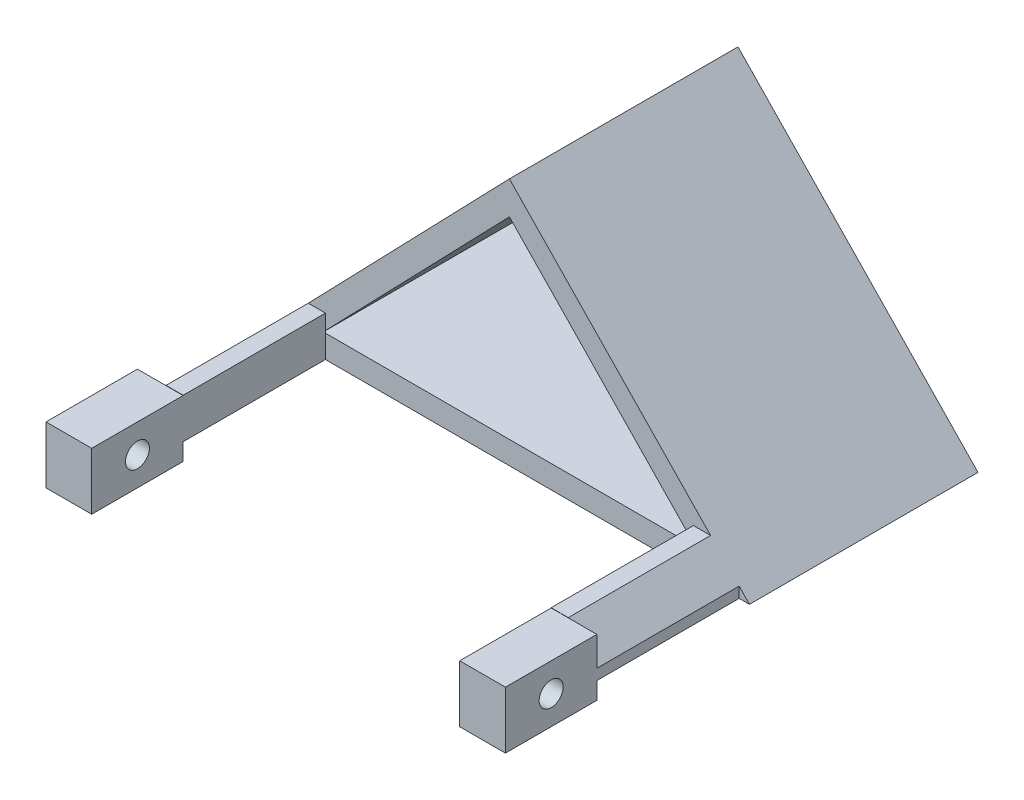
SolidWorks part; units mm, degrees
ref_plane "Front Plane" through (0, 0, 0) normal (0, 0, 1) x (1, 0, 0)
ref_plane "Top Plane" through (0, 0, 0) normal (0, 1, 0) x (1, 0, 0)
ref_plane "Right Plane" through (0, 0, 0) normal (1, 0, 0) x (0, 0, -1)
sketch "Sketch1" plane through (0, 0, 0) normal (0, 0, 1) x (1, 0, 0)
  line L1 (0, 0) -> (-42, -43.4923)
  line L2 (0, -1000.3549) -> (0, 48999.6451) construction
  line L3 (-32.5766, -39.4923) -> (0, -5.7582)
  line L4 (32.5766, -39.4923) -> (0, -5.7582)
  line L5 (0, 0) -> (42, -43.4923)
  line L7 (-42, -43.4923) -> (42, -43.4923)
  line L8 (-32.5766, -39.4923) -> (32.5766, -39.4923)
  line L9 (-34, -35.208) -> (34, -35.208) construction
  dimension "D1" = 88
  dimension "D2" = 4
  dimension "D3" = 4
  dimension "D4" = 68
  dimension "D5" = 8
extrude "Boss-Extrude1" add sketch "Sketch1" along normal mid plane 40
sketch "Sketch2" plane through (0, 0, 0) normal (1, 0, 0) x (0, 0, -1)
  line L0 (0, -1034.3624) -> (0, 48965.6376) construction
  line L1 (-20, -43.4923) -> (20, -43.4923) construction
  line L2 (-3.5, -43.4923) -> (-3.5, -66.9923)
  line L3 (-3.5, -66.9923) -> (-9, -66.9923)
  line L4 (-9, -66.9923) -> (-9, -70.4923)
  line L5 (-9, -70.4923) -> (9, -70.4923)
  line L6 (9, -66.9923) -> (9, -70.4923)
  line L7 (3.5, -66.9923) -> (9, -66.9923)
  line L8 (3.5, -43.4923) -> (3.5, -66.9923)
  line L9 (3.5, -43.4923) -> (-3.5, -43.4923)
  point P5 (0, -43.4923)
  dimension "D1" = 7
  dimension "D2" = 3.5
  dimension "D3" = 27
  dimension "D4" = 18
extrude "Boss-Extrude2" [suppressed] add sketch "Sketch2" along normal blind 6 from vertex starting at point (-42, -43.4923, 0)
sketch "Sketch4" [suppressed] plane through (0, 0, 0) normal (1, 0, 0) x (0, 0, -1)
  line L0 (-20, -38.4859) -> (20, -38.4859) construction
  line L1 (3.5, -38.4859) -> (13.5, -38.4859)
  line L2 (3.5, -38.4859) -> (3.5, -65.4859)
  line L3 (3.5, -65.4859) -> (13.5, -65.4859)
  line L4 (13.5, -38.4859) -> (13.5, -65.4859)
  line L5 (-9, -65.4859) -> (9, -65.4859) construction
  line L7 (-11, -38.4859) -> (-18.5, -38.4859)
  line L8 (-11, -38.4859) -> (-11, -65.4859)
  line L9 (-11, -65.4859) -> (-18.5, -65.4859)
  line L10 (-18.5, -38.4859) -> (-18.5, -65.4859)
  line L11 (-9, -61.9859) -> (-9, -65.4859) construction
  dimension "D1" = 10
  dimension "D2" = 2
  dimension "D3" = 7.5
extrude "Boss-Extrude3" [suppressed] add sketch "Sketch4" against normal blind 6 from vertex starting at point (42, -43.4923, 20)
sketch "Sketch5" plane through (0, 0, 20) normal (0, 0, 1) x (1, 0, 0)
  line L1 (0, 0) -> (-42, -43.4923) construction
  line L2 (-35.2, -36.4507) -> (-32.2, -36.4507)
  line L3 (-32.2, -36.4507) -> (-32.2, -43.4923)
  line L4 (-42, -43.4923) -> (42, -43.4923) construction
  line L5 (-32.2, -43.4923) -> (-40.2, -43.4923)
  line L6 (-40.2, -43.4923) -> (-40.2, -41.6283)
  line L7 (-40.2, -41.6283) -> (-35.2, -36.4507)
  line L8 (-40.4, 38.5755) -> (-40.4, -71.4923) construction
  dimension "D1" = 8
  dimension "D2" = 3
  dimension "D3" = 0.2
extrude "Boss-Extrude4" add sketch "Sketch5" along normal up to surface (24.9 mm away)
sketch "Sketch6" plane through (0, 0, 44.9) normal (0, 0, 1) x (1, 0, 0)
  line L0 (-40.2, -41.6283) -> (-40.2, -43.4923) construction
  line L1 (-32.2, -46.4923) -> (-40.2, -46.4923)
  line L2 (-32.2, -46.4923) -> (-32.2, -36.4923)
  line L3 (-32.2, -36.4923) -> (-40.2, -36.4923)
  line L4 (-40.2, -46.4923) -> (-40.2, -36.4923)
  line L5 (-32.2, -43.4923) -> (-32.2, -36.4507) construction
  line L6 (-40.2, -43.4923) -> (-32.2, -43.4923) construction
  dimension "D1" = 10
  dimension "D2" = 3
extrude "Boss-Extrude5" add sketch "Sketch6" along normal blind 16
sketch "Sketch7" plane through (-32.2, 0, 0) normal (1, 0, 0) x (0, 0, -1)
  line L0 (-60.9, -36.4923) -> (-44.9, -36.4923) construction
  line L1 (-60.9, -46.4923) -> (-60.9, -36.4923) construction
  circle A0 centre (-52.9, -41.4923) radius 2.1
  point P5 (-52.9, -36.4923)
  point P8 (-60.9, -41.4923)
  dimension "D1" = 4.2
extrude "Cut-Extrude1" cut sketch "Sketch7" against normal through all
mirror "Mirror1" about plane through (0, 0, 0) normal (1, 0, 0) of "Cut-Extrude1", "Boss-Extrude5", "Boss-Extrude4"
equation "\"width\"= 24"
equation "\"thk\"= 3"
equation "\"holesize\"= 4.2"
equation "\"holedistance\"= ( 20 + 12 ) / 2"
equation "\"threaded_hole\"= 3.9"
equation "\"fillet_radius\"= 2"
equation "\"ground_clearance\"= 25"
equation "\"tire_thk\"= 3"
equation "\"innerwheel_diam\" = \"wheel_diam\"-2*\"tire_thk\""
equation "\"innerwheel_thk\"= 8"
equation "\"wheel_diam\"= 2*(\"width\"/2+\"ground_clearance\")"
equation "\"coloursensor_holesize\"= 2.65"
equation "\"hole_to_edge\" = 4"
equation "\"D1@Sketch7\"=\"holesize\""
